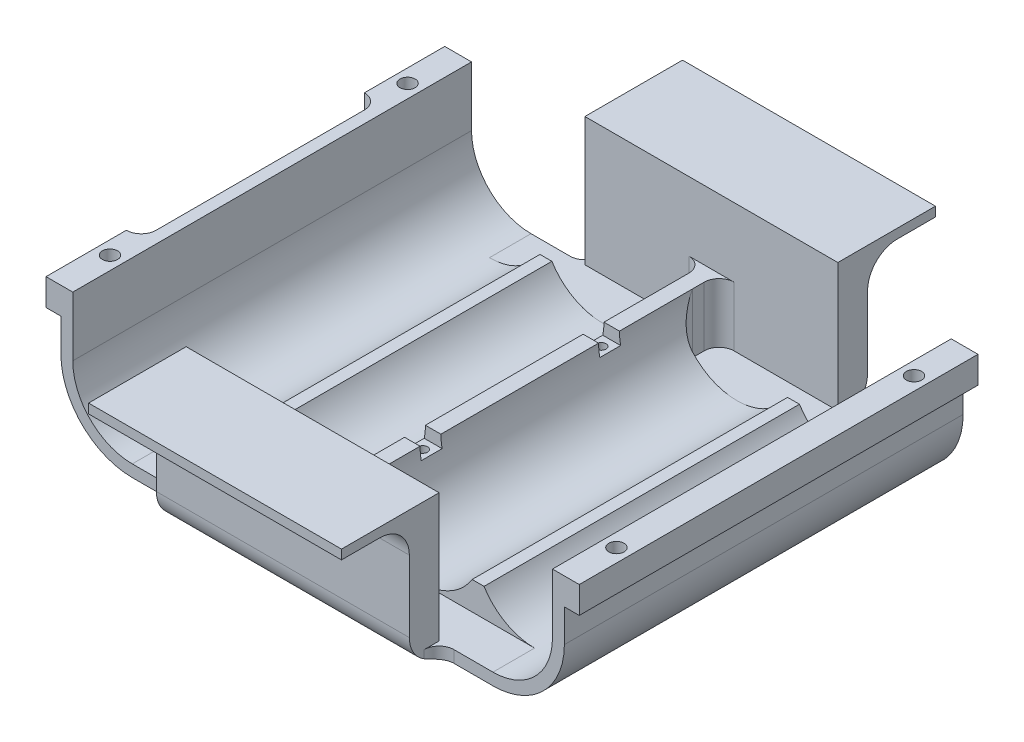
SolidWorks part; units mm, degrees
material "6061-T6 (SS)"
ref_plane "Front" through (0, 0, 0) normal (0, 0, 1) x (1, 0, 0)
ref_plane "Top" through (0, 0, 0) normal (0, 1, 0) x (1, 0, 0)
ref_plane "Right" through (0, 0, 0) normal (1, 0, 0) x (0, 0, -1)
sketch "Sketch1" plane through (0, 0, 0) normal (0, 0, 1) x (1, 0, 0)
  line L0 (0, 0) -> (4.5, 0)
  line L1 (23, -15.2678) -> (25, -15.2678)
  line L2 (43.5, -10) -> (46.1, -10)
  line L3 (0, 0) -> (0, -4.5)
  line L5 (44.8, -7.7789) -> (44.8, -24.8233) construction
  line L7 (89.6, 0) -> (89.6, -4.5)
  line L8 (66.6, -15.2678) -> (64.6, -15.2678)
  line L9 (89.6, 0) -> (85.1, 0)
  line L11 (4.5, -10) -> (4.5, 0)
  line L12 (85.1, -10) -> (85.1, 0)
  line L20 (14.5, -22) -> (75.1, -22)
  line L22 (2.5, -10) -> (2.5, -4.5)
  line L23 (0, -4.5) -> (2.5, -4.5)
  line L24 (89.6, -4.5) -> (87.1, -4.5)
  line L25 (87.1, -10) -> (87.1, -4.5)
  arc A1 (25, -15.2678) -> (43.5, -10) centre (33.5, -10) ccw
  arc A2 (2.5, -10) -> (14.5, -22) centre (14.5, -10) ccw
  arc A3 (64.6, -15.2678) -> (46.1, -10) centre (56.1, -10) cw
  arc A6 (23, -15.2678) -> (4.5, -10) centre (14.5, -10) cw
  arc A7 (66.6, -15.2678) -> (85.1, -10) centre (75.1, -10) ccw
  arc A10 (87.1, -10) -> (75.1, -22) centre (75.1, -10) cw
  point P38 (87.5, -7)
  point P48 (44.8, -22)
  dimension "D2" = 10
  dimension "D8" = 19
  dimension "D4" = 10
  dimension "D10" = 2
  dimension "D9" = 12
  dimension "D5" = 10
  dimension "D7" = 4.5
  dimension "D12" = 10
  dimension "D13" = 2.6
  dimension "D14" = 4.5
extrude "Boss-Extrude1" add sketch "Sketch1" along normal mid plane 67
ref_plane "Plane1" through (44.8, 0, 0) normal (-1, 0, 0) x (0, 0, 1)
sketch "Sketch8" plane through (0, 0, 0) normal (0, 1, 0) x (1, 0, 0)
  line L0 (87.35, 33.5) -> (87.35, -33.5) construction
  line L1 (89.6, 33.5) -> (85.1, 33.5) construction
  line L2 (89.6, -33.5) -> (85.1, -33.5) construction
  line L4 (85.1, -33.5) -> (85.1, 33.5) construction
  point P8 (87.35, -18.5)
  point P9 (87.35, 18.5)
  dimension "D1" = 2.25
  dimension "D2" = 15
  dimension "D3" = 15
sketch "Sketch9" plane through (44.8, 0, 0) normal (-1, 0, 0) x (0, 0, 1)
  line L0 (33.5, -22) -> (38.5, -22)
  line L1 (38.5, -22) -> (38.5, 0)
  line L2 (38.5, 0) -> (49.9, 0)
  line L3 (49.9, 0) -> (49.9, 1.58)
  line L4 (49.9, 1.58) -> (33.5, 1.58)
  line L5 (33.5, 1.58) -> (33.5, -22)
  line L6 (33.5, 0) -> (-33.5, 0) construction
  dimension "D1" = 1.58
  dimension "D2" = 16.4
  dimension "D3" = 5
extrude "Boss-Extrude2" add sketch "Sketch9" along normal mid plane 42.5
mirror "Mirror1" about plane through (0, 0, 0) normal (0, 0, 1) of "Boss-Extrude2"
fillet "Fillet3" radius 5 4 edges at (44.8, -22, -38.5) (44.8, 0, -38.5) (44.8, 0, 38.5) (44.8, -22, 38.5)
sketch "Sketch14" plane through (0, 0, 0) normal (0, 1, 0) x (1, 0, 0)
  line L0 (0, 20) -> (2.5, 20)
  line L1 (0, -33.5) -> (0, 33.5) construction
  line L2 (2.5, 20) -> (2.5, -20)
  line L3 (2.5, -20) -> (0, -20)
  line L4 (0, -20) -> (0, 20)
  point P4 (0, 0)
  dimension "D1" = 2.5
  dimension "D2" = 40
extrude "Cut-Extrude3" cut sketch "Sketch14" against normal up to next
hole_wizard "M2x0.4 Tapped Hole1" positions "Sketch15" profile "Sketch16" tap size "M2x0.4" standard "ANSI Metric" end condition up to next
sketch "Sketch15" plane through (0, -10, 0) normal (0, 1, 0) x (1, 0, 0)
  line L1 (46.1, -33.5) -> (46.1, 33.5) construction
  line L2 (-40.9116, 0) -> (40.9116, 0) construction
  point P0 (44.8, 15)
  point P2 (44.8, -15)
  dimension "D1" = 1.3
  dimension "D2" = 1.3
  dimension "D3" = 30
  dimension "D4" = 15
sketch "Sketch16" plane through (44.8, -10, -15) normal (1, 0, 0) x (0, 0, 1)
  line L0 (0, 0) -> (0, 12)
  line L1 (0, 12) -> (0.8, 12)
  line L2 (0.8, 12) -> (0.8, 0)
  line L5 (0.8, 0) -> (0, 0)
  line L11 (0, -6.35) -> (0, 107.95) construction
  dimension "Thru Tap Drill Dia." = 1.6
  dimension "Thru Tap Drill Depth" = 12
cosmetic thread "Hole Thread5" parameters "D2"=2
cosmetic thread "Hole Thread6" parameters "D2"=2
hole_wizard "Tapped Hole for M2.5x0.45 Helicoil1" positions "Sketch20" profile "Sketch21" tap size "M2.5x0.45" standard "Helicoil® Metric"
sketch "Sketch20" plane through (0, 0, 0) normal (0, 1, 0) x (1, 0, 0)
  line L0 (-40.9116, 0) -> (40.9116, 0) construction
  line L1 (4.5, -33.5) -> (0, -33.5) construction
  line L2 (89.6, -33.5) -> (85.1, -33.5) construction
  line L3 (0, -33.5) -> (0, -20) construction
  point P0 (2.25, 25)
  point P2 (2.25, -25)
  point P4 (87.35, -25)
  point P6 (87.35, 25)
  point P22 (2.25, -33.5)
  point P26 (87.35, -33.5)
  dimension "D1" = 50
  dimension "D2" = 25
  dimension "D3" = 50
  dimension "D4" = 25
  dimension "D5" = 2.25
cosmetic thread "Hole Thread1" parameters "D1"=4.5, "D2"=3.145
cosmetic thread "Hole Thread2" parameters "D1"=4.5, "D2"=3.145
cosmetic thread "Hole Thread3" parameters "D1"=4.5, "D2"=3.145
cosmetic thread "Hole Thread4" parameters "D1"=4.5, "D2"=3.145
sketch "Sketch21" plane through (2.25, 0, -25) normal (1, 0, 0) x (0, 0, 1)
  line L0 (0, 0) -> (0, 5.2661)
  line L1 (0, 5.2661) -> (1.275, 4.5)
  line L2 (1.275, 4.5) -> (1.275, 0)
  line L5 (1.275, 0) -> (0, 0)
  line L10 (0, 5.2661) -> (-1.275, 4.5) construction
  line L11 (0, -6.35) -> (0, 107.95) construction
  dimension "Tap Drill Dia." = 2.55
  dimension "Tap Drill Depth" = 4.5
  dimension "Drill Angle" = 118
sketch "Sketch22" plane through (0, 1.58, 0) normal (0, 1, 0) x (1, 0, 0)
  line L0 (43.5, 33.5) -> (43.5, 26.5)
  line L2 (14.5, 33.5) -> (14.5, 26.5)
  line L4 (75.1, 33.5) -> (75.1, 26.5)
  line L5 (43.5, -33.5) -> (43.5, 33.5) construction
  line L7 (14.5, -33.5) -> (14.5, -26.5)
  line L9 (75.1, -33.5) -> (75.1, -26.5)
  line L10 (43.5, 26.5) -> (14.5, 26.5)
  line L11 (46.1, 33.5) -> (46.1, 26.5)
  line L12 (4.5, -33.5) -> (4.5, 33.5) construction
  line L13 (46.1, -33.5) -> (46.1, 33.5) construction
  line L14 (46.1, 26.5) -> (75.1, 26.5)
  line L15 (14.5, 33.5) -> (43.5, 33.5)
  line L16 (46.1, 33.5) -> (75.1, 33.5)
  line L17 (14.5, -26.5) -> (43.5, -26.5)
  line L18 (43.5, -26.5) -> (43.5, -33.5)
  line L19 (43.5, -33.5) -> (14.5, -33.5)
  line L20 (75.1, -26.5) -> (46.1, -26.5)
  line L21 (46.1, -26.5) -> (46.1, -33.5)
  line L22 (46.1, -33.5) -> (75.1, -33.5)
  dimension "D1" = 7
  dimension "D2" = 60.6
  dimension "D3" = 10
extrude "Cut-Extrude4" cut sketch "Sketch22" against normal blind 21.58
fillet "Fillet5" radius 2.5 14 edges at (23.55, -21, -33.5) (66.05, -21, -33.5) (66.05, -21, 33.5) (23.55, -21, 33.5) (2.5, -2.25, 20) (2.5, -2.25, -20) (43.5, -15, -26.5) (43.5, -15, -33.5) (43.5, -15, 26.5) (43.5, -15, 33.5) (46.1, -15, 33.5) (46.1, -15, 26.5) (46.1, -15, -26.5) (46.1, -15, -33.5)
sketch "Sketch23" plane through (0, -10, 0) normal (0, 1, 0) x (1, 0, 0)
  line L0 (23.55, 33.5) -> (66.05, 33.5) construction
  line L1 (38.5471, 16.75) -> (51.1994, 16.75)
  line L2 (38.5471, 16.75) -> (38.5471, 13.25)
  line L3 (38.5471, 13.25) -> (51.1994, 13.25)
  line L4 (51.1994, 16.75) -> (51.1994, 13.25)
  line L5 (38.842, -13.25) -> (49.8605, -13.25)
  line L6 (38.842, -13.25) -> (38.842, -16.75)
  line L7 (38.842, -16.75) -> (49.8605, -16.75)
  line L8 (49.8605, -13.25) -> (49.8605, -16.75)
  line L9 (23.55, -33.5) -> (66.05, -33.5) construction
  point P8 (38.5471, 15)
  point P11 (38.842, -15)
  dimension "D1" = 3.5
  dimension "D2" = 3.5
  dimension "D3" = 18.5
  dimension "D4" = 18.5
extrude "Cut-Extrude5" cut sketch "Sketch23" against normal blind 2
